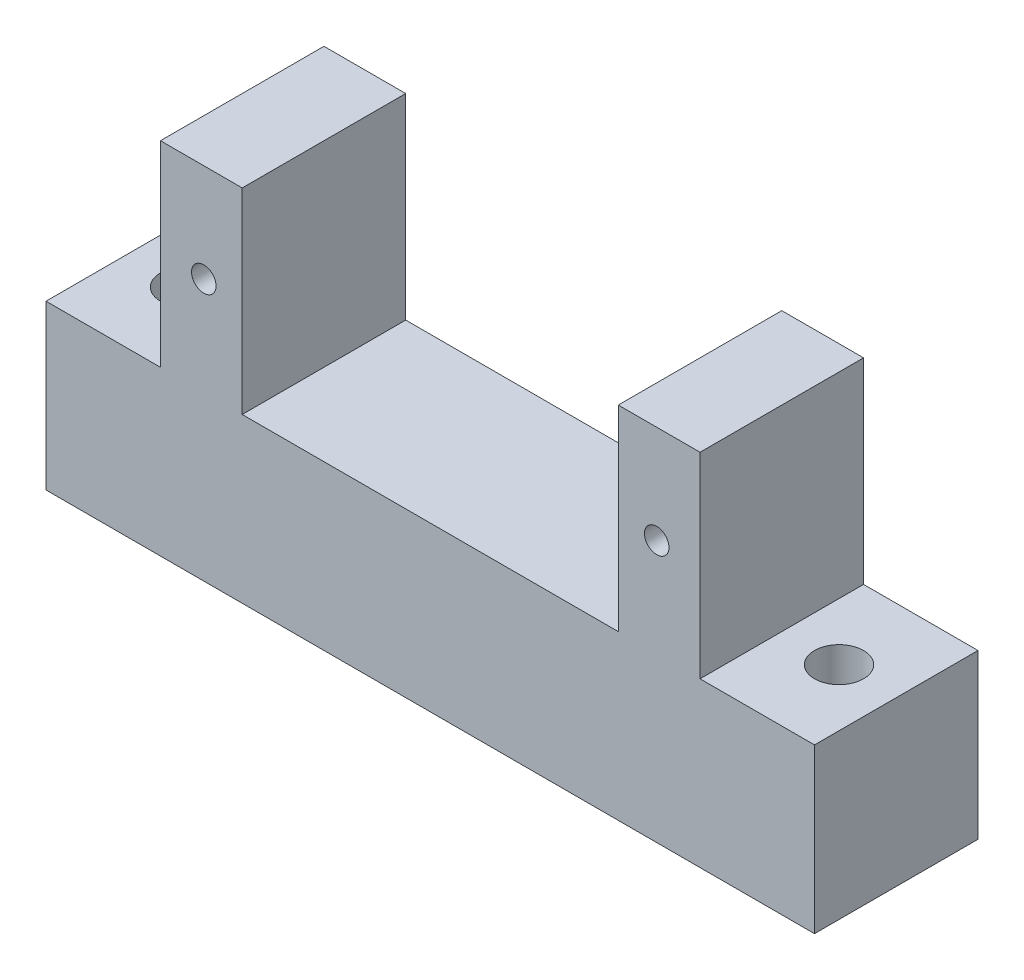
SolidWorks part; units mm, degrees
ref_plane "Спереди" through (0, 0, 0) normal (0, 0, 1) x (1, 0, 0)
ref_plane "Сверху" through (0, 0, 0) normal (0, 1, 0) x (1, 0, 0)
ref_plane "Справа" through (0, 0, 0) normal (1, 0, 0) x (0, 0, -1)
other "Configuration Table"
sketch "Эскиз1" plane through (0, 0, 0) normal (0, 1, 0) x (1, 0, 0)
  line L0 (0, 0) -> (77.2489, 0) construction
  line L1 (-20, 0) -> (-20, -10) construction
  line L2 (-11.5, 0) -> (11.5, 0)
  line L3 (-11.5, 0) -> (-11.5, -10)
  line L4 (-11.5, -10) -> (11.5, -10)
  line L5 (11.5, 0) -> (11.5, -10)
  line L6 (-11.5, 0) -> (-16.5, 0)
  line L7 (-11.5, 0) -> (-11.5, -10)
  line L8 (-11.5, -10) -> (-16.5, -10)
  line L9 (-16.5, 0) -> (-16.5, -10)
  line L10 (11.5, 0) -> (16.5, 0)
  line L11 (11.5, 0) -> (11.5, -10)
  line L12 (11.5, -10) -> (16.5, -10)
  line L13 (16.5, 0) -> (16.5, -10)
  line L14 (-16.5, 0) -> (-23.5, 0)
  line L15 (-16.5, 0) -> (-16.5, -10)
  line L16 (-16.5, -10) -> (-23.5, -10)
  line L17 (-23.5, 0) -> (-23.5, -10)
  line L18 (16.5, 0) -> (23.5, 0)
  line L19 (16.5, 0) -> (16.5, -10)
  line L20 (16.5, -10) -> (23.5, -10)
  line L21 (23.5, 0) -> (23.5, -10)
  line L22 (-23.5, -5) -> (-16.5, -5) construction
  line L23 (16.5, -5) -> (23.5, -5) construction
  line L24 (20, 0) -> (20, -10) construction
  circle A0 centre (-20, -5) radius 1.5
  circle A1 centre (20, -5) radius 1.5
  dimension "D5" = 3
  dimension "D1" = 23
  dimension "D2" = 5
  dimension "D3" = 10
  dimension "D4" = 40
  dimension "D6" = 47
extrude "Бобышка-Вытянуть1" add sketch "Эскиз1" along normal blind 3 and the other way blind 7 contours L14 L17 L16 L9 A0 | L5 L2 L3 L4 | L21 L18 L13 L20 A1 region at (0, 0, 5) region at (-16.6221, 0, 5) region at (20, 0, 0.1221)
extrude "Бобышка-Вытянуть2" add sketch "Эскиз1<4>" along normal blind 15 and the other way blind 7 contours L6 L9 L8 L3 | L13 L10 L5 L12 region at (-14, 0, 5) region at (14, 0, 5)
sketch "Эскиз1<4>" plane through (0, 0, 0) normal (0, 1, 0) x (1, 0, 0) same geometry as "Эскиз1"
sketch "Эскиз2" plane through (0, 0, 0) normal (0, 0, -1) x (-1, 0, 0)
  line L0 (11.5, 15) -> (16.5, 15) construction
  line L1 (-11.5, 15) -> (-16.5, 15) construction
  line L2 (-13.85, 3) -> (-11.5, 3) construction
  line L3 (13.85, 3) -> (11.5, 3) construction
  line L4 (-13.85, 15) -> (-13.85, 3) construction
  line L5 (13.85, 15) -> (13.85, 3) construction
  circle A0 centre (-13.85, 9) radius 0.75
  circle A1 centre (13.85, 9) radius 0.75
  dimension "D1" = 1.5
  dimension "D2" = 27.7
extrude "Вырез-Вытянуть1" cut sketch "Эскиз2" against normal blind 15
